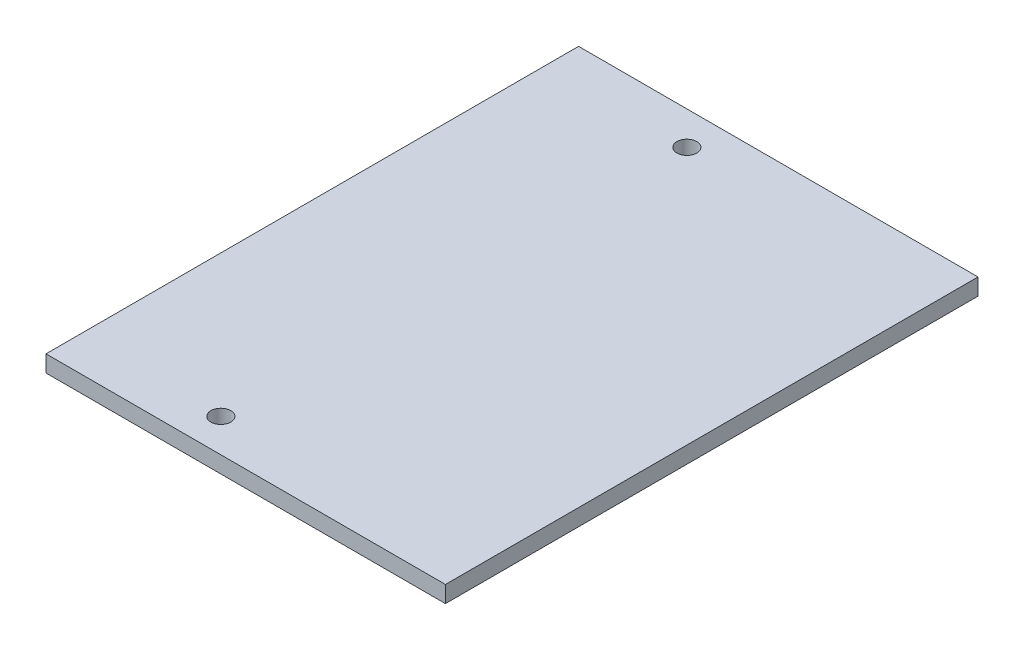
SolidWorks part; units mm, degrees
material "Custom Plastic"
ref_plane "Front Plane" through (0, 0, 0) normal (0, 0, 1) x (1, 0, 0)
ref_plane "Top Plane" through (0, 0, 0) normal (0, 1, 0) x (1, 0, 0)
ref_plane "Right Plane" through (0, 0, 0) normal (1, 0, 0) x (0, 0, -1)
sketch "Sketch1" plane through (0, 0, 0) normal (0, 1, 0) x (1, 0, 0)
  line L1 (-38.1, -50.8) -> (38.1, -50.8)
  line L2 (-38.1, -50.8) -> (-38.1, 50.8)
  line L3 (-38.1, 50.8) -> (38.1, 50.8)
  line L4 (38.1, -50.8) -> (38.1, 50.8)
  line L5 (-38.1, -50.8) -> (38.1, 50.8) construction
  line L6 (-38.1, 50.8) -> (38.1, -50.8) construction
  point P0 (0, 0)
  dimension "D1" = 76.2
  dimension "D2" = 101.6
extrude "Boss-Extrude1" add sketch "Sketch1" along normal blind 3.175
hole_wizard "#6 Clearance Hole1" positions "3DSketch1" profile "Sketch2" hole size "#6" standard "ANSI Inch" end condition through all
sketch3d "3DSketch1"
  line L2 (-11.0896, 3.175, -50.8) -> (-11.0896, 3.175, 50.8) construction
  line L3 (38.1, 3.175, -50.8) -> (-38.1, 3.175, -50.8) construction
  line L4 (-38.1, 3.175, 50.8) -> (38.1, 3.175, 50.8) construction
  line L6 (38.1, 3.175, 50.8) -> (38.1, 3.175, -50.8) construction
  point P0 (-11.0896, 3.175, -44.45)
  point P2 (-11.0896, 3.175, 44.45)
  dimension "D3" = 6.35
  dimension "D2" = 6.35
  dimension "D1" = 49.1896
sketch "Sketch2" plane through (-11.0896, 3.175, -44.45) normal (1, 0, 0) x (0, 0, 1)
  line L0 (0, 0) -> (0, 3.175)
  line L1 (0, 3.175) -> (1.8986, 3.175)
  line L2 (1.8986, 3.175) -> (1.8986, 0)
  line L5 (1.8986, 0) -> (0, 0)
  line L11 (0, -6.35) -> (0, 107.95) construction
  dimension "Thru Hole Dia." = 3.7973
  dimension "Thru Hole Depth" = 3.175
equation "\"D3@3DSketch1\"=\"D2@3DSketch1\""
